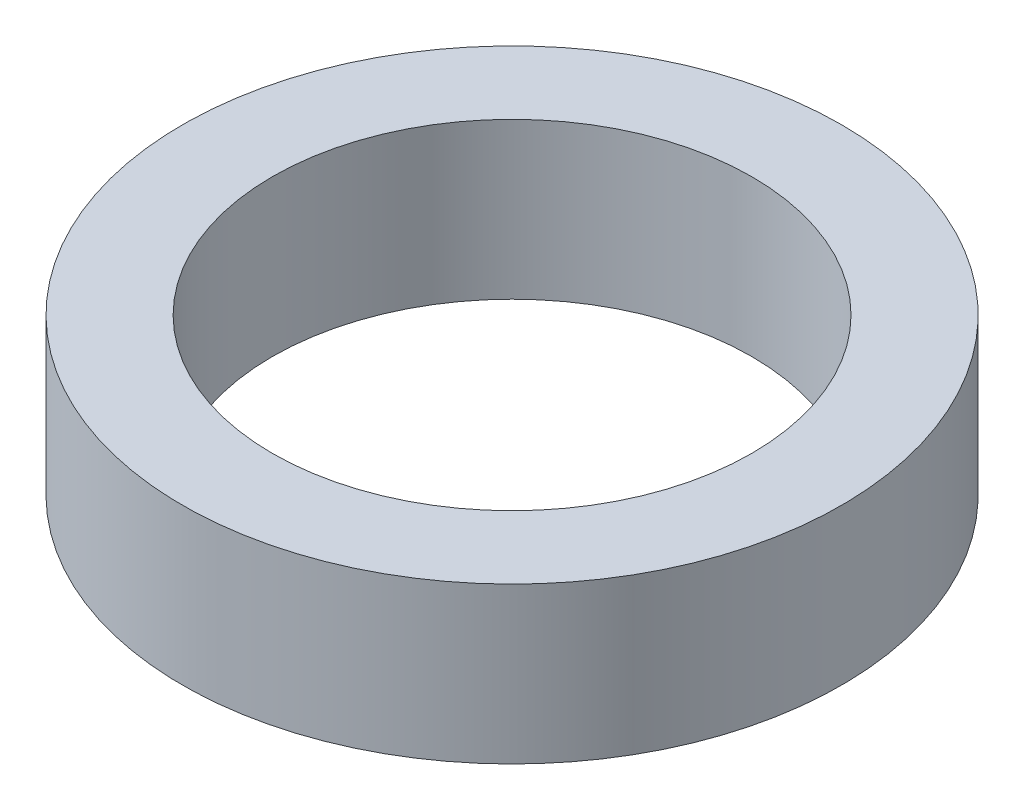
SolidWorks part; units mm, degrees
ref_plane "Front Plane" through (0, 0, 0) normal (0, 0, 1) x (1, 0, 0)
ref_plane "Top Plane" through (0, 0, 0) normal (0, 1, 0) x (1, 0, 0)
ref_plane "Right Plane" through (0, 0, 0) normal (1, 0, 0) x (0, 0, -1)
sketch "Sketch1" plane through (0, 0, 0) normal (0, 1, 0) x (1, 0, 0)
  circle A0 centre (0, 0) radius 55
  dimension "FLANGE_OD" = 110
extrude "Boss-Extrude1" add sketch "Sketch1" along normal blind 26
sketch "Sketch2" plane through (0, 0, 0) normal (0, 1, 0) x (1, 0, 0)
  circle A0 centre (0, 0) radius 40
  dimension "BORE_D" = 80
extrude "Cut-Extrude1" cut sketch "Sketch2" along normal through all
sketch "Sketch3" plane through (0, 26, 0) normal (0, 1, 0) x (1, 0, 0)
  circle A0 centre (0, 0) radius 25.8714 construction
  circle A1 centre (-25.8714, 0) radius 1.6316
  dimension "BOLT_D" = 3.2631
  dimension "BOLT_PCD" = 51.7428
extrude "Cut-Extrude2" cut sketch "Sketch3" against normal blind 19.205 rebuild error yes
pattern_circular "CirPattern1" count 8 over 360 rebuild error yes
